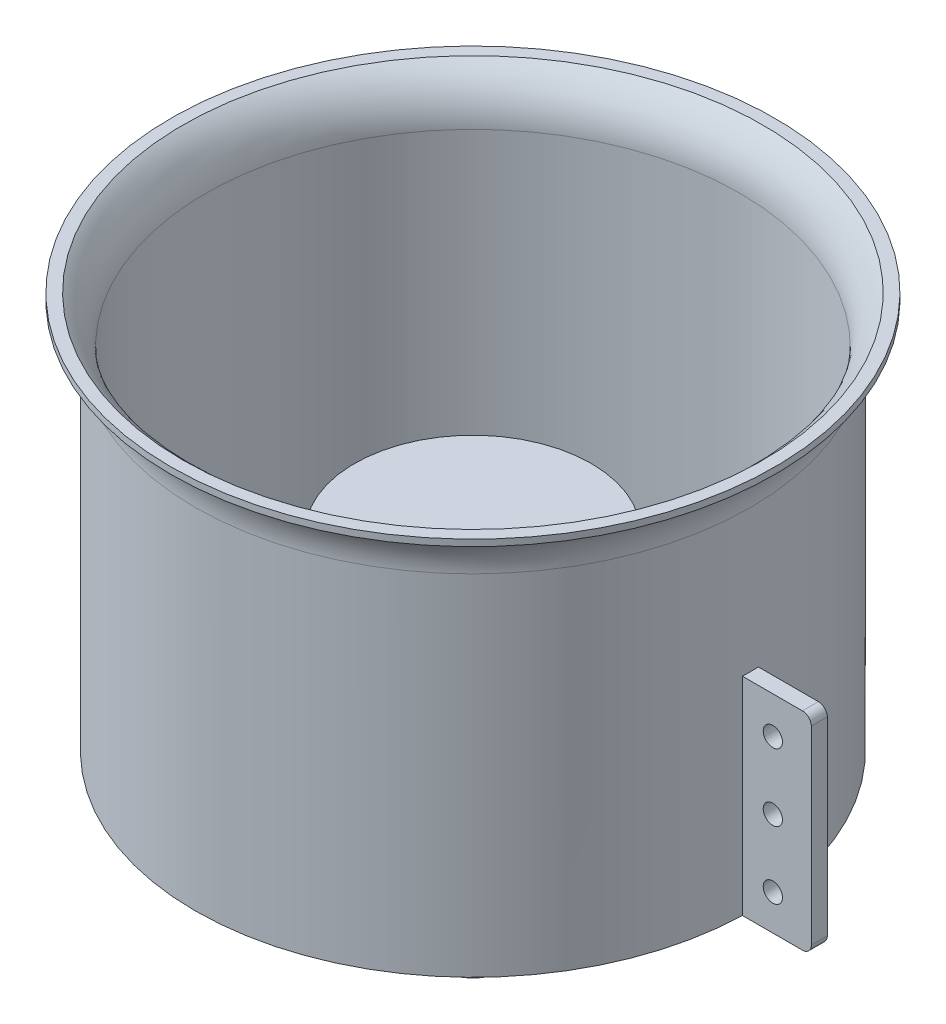
SolidWorks part; units mm, degrees
ref_plane "Front Plane" through (0, 0, 0) normal (0, 0, 1) x (1, 0, 0)
ref_plane "Top Plane" through (0, 0, 0) normal (0, 1, 0) x (1, 0, 0)
ref_plane "Right Plane" through (0, 0, 0) normal (1, 0, 0) x (0, 0, -1)
ref_axis "Axis1" through (0, 55, 0) along (0, -1, 0)
sketch "Sketch1" plane through (0, 0, 0) normal (0, 0, 1) x (1, 0, 0)
  line L0 (-45.075, 0) -> (-45.075, 59)
  line L1 (-49, 67) -> (-51, 67)
  line L2 (-46.875, 59) -> (-46.875, 0)
  line L3 (-46.875, 0) -> (-45.075, 0)
  line L4 (-51, 67) -> (-51, 65.9)
  line L5 (-51, 65.9) -> (-49.5, 65.9)
  line L6 (0, 55) -> (0, -55) construction
  arc A0 (-45.075, 59) -> (-49, 67) centre (-55.1904, 59) ccw
  arc A1 (-49.5, 65.9) -> (-46.875, 59) centre (-57.2561, 59) cw
  dimension "D1" = 51
  dimension "D2" = 49
  dimension "D3" = 46.875
  dimension "D4" = 1.8
  dimension "D5" = 1.1
  dimension "D6" = 1.5
  dimension "D7" = 8
  dimension "D8" = 67
revolve "Revolve1" add sketch "Sketch1" angle 360 about axis through (0, 55, 0) along (0, -1, 0)
sketch "Sketch2" plane through (0, 0, 0) normal (0, -1, 0) x (1, 0, 0)
  circle A0 centre (0, 0) radius 20
  dimension "D1" = 40
extrude "Boss-Extrude1" add sketch "Sketch2" against normal blind 32 separate body
sketch "Sketch3" plane through (0, 0, 0) normal (0, -1, 0) x (1, 0, 0)
  circle A0 centre (0, 0) radius 17.5
  dimension "D1" = 35
extrude "Boss-Extrude2" add sketch "Sketch3" along normal blind 20
sketch "Sketch4" plane through (0, -20, 0) normal (0, -1, 0) x (1, 0, 0)
  circle A0 centre (0, 0) radius 6
  dimension "D1" = 12
extrude "Boss-Extrude3" add sketch "Sketch4" along normal blind 9
sketch "Sketch5" plane through (0, 0, 0) normal (0, 0, 1) x (1, 0, 0)
  line L0 (-46.875, 0) -> (46.875, 0) construction
  line L1 (-45.075, 35) -> (-58.5, 35)
  line L2 (-45.075, 35) -> (-45.075, 0)
  line L3 (-45.075, 0) -> (-58.5, 0)
  line L4 (-58.5, 35) -> (-58.5, 0)
  line L5 (0, 55) -> (0, -55) construction
  line L6 (-45.075, 0) -> (-45.075, 20.6591) construction
  dimension "D1" = 35
  dimension "D2" = 58.5
extrude "Boss-Extrude4" add sketch "Sketch5" along normal blind 1.35 and the other way blind 1.35
sketch "Sketch6" plane through (0, 0, 1.35) normal (0, 0, 1) x (1, 0, 0)
  line L0 (-52, 28.75) -> (-52, 6) construction
  line L1 (-58.5, 0) -> (-46.8556, 0) construction
  line L3 (0, 55) -> (0, -55) construction
  circle A0 centre (-52, 6) radius 1.625
  circle A1 centre (-52, 17.375) radius 1.625
  circle A2 centre (-52, 28.75) radius 1.625
  dimension "D1" = 3.25
  dimension "D2" = 22.75
  dimension "D3" = 6
  dimension "D4" = 52
extrude "Cut-Extrude1" cut sketch "Sketch6" against normal through all
fillet "Fillet1" radius 1.5 2 edges at (-58.5, 35, 0) (-58.5, 0, 0)
pattern_circular "CirPattern1" count 2 every 180 about axis through (0, 55, 0) along (0, -1, 0) of "Fillet1", "Cut-Extrude1", "Boss-Extrude4"
